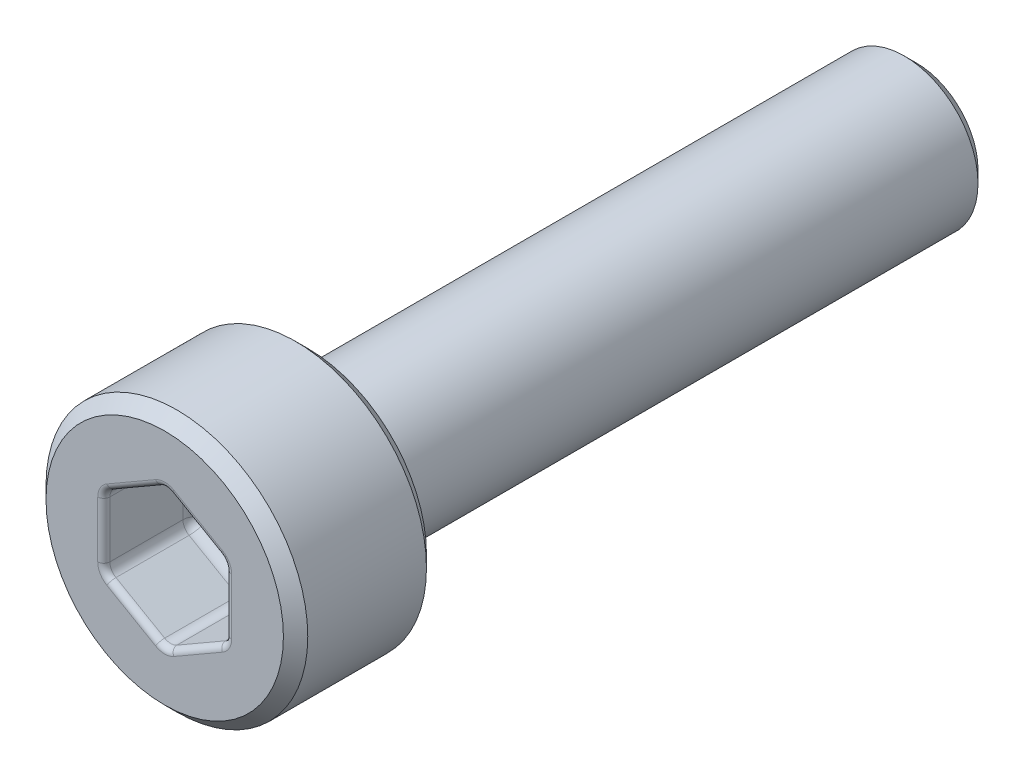
SolidWorks part; units mm, degrees
material "1.4000 (X6Cr13)"
ref_plane "Ebene vorne" through (0, 0, 0) normal (0, 0, 1) x (1, 0, 0)
ref_plane "Ebene oben" through (0, 0, 0) normal (0, 1, 0) x (1, 0, 0)
ref_plane "Ebene rechts" through (0, 0, 0) normal (1, 0, 0) x (0, 0, -1)
sketch "Skizze1" plane through (0, 0, 0) normal (1, 0, 0) x (0, 0, -1)
  line L0 (-21.9199, 0) -> (33.7608, 0) construction
  line L1 (0, 13.9907) -> (0, -9.4798) construction
  line L2 (-2.35, 0) -> (-2.35, 2.15)
  line L3 (-2.35, 2.15) -> (0, 2.15)
  line L4 (0, 2.15) -> (0, 1.21)
  line L5 (0, 1.21) -> (10, 1.21)
  line L6 (10, 1.21) -> (10, 0)
  line L7 (10, 0) -> (-2.35, 0)
  dimension "D1" = 2.42
  dimension "D2" = 2.35
  dimension "D3" = 4.3
  dimension "D4" = 10
revolve "Rotation1" add sketch "Skizze1" angle 360 about L0
sketch "Skizze2" plane through (0, 0, 2.35) normal (0, 0, 1) x (1, 0, 0)
  line L0 (0, 8.6995) -> (0, -7.3778) construction
  line L1 (1, -0.5774) -> (1, 0.5774)
  line L2 (1, 0.5774) -> (0, 1.1547)
  line L3 (0, 1.1547) -> (-1, 0.5774)
  line L4 (-1, 0.5774) -> (-1, -0.5774)
  line L5 (-1, -0.5774) -> (0, -1.1547)
  line L6 (0, -1.1547) -> (1, -0.5774)
  circle A0 centre (0, 0) radius 1 construction
  dimension "D1" = 2
extrude "Schnitt-Linear austragen1" cut sketch "Skizze2" against normal blind 1.5
chamfer "Fase1" distance 0.2 angle 45 3 edges at (2.15, 0, 2.35) (2.15, 0, 0) (1.21, 0, -10)
fillet "Verrundung1" radius 0.2 13 edges at (-0.5, -0.866, 0.85) (-1, 0, 0.85) (-0.5, 0.866, 0.85) (0.5, 0.866, 0.85) (1, 0, 0.85) (0.5, -0.866, 0.85) (-1, -0.5774, 1.6) (0, -1.1547, 1.6) (1, -0.5774, 1.6) (1, 0.5774, 1.6) (0, 1.1547, 1.6) (-1, 0.5774, 1.6) (1.21, 0, 0)
fillet "Verrundung2" radius 0.1 12 edges at (0.9732, -0.5619, 2.35) (0.5, -0.866, 2.35) (0, -1.1238, 2.35) (-0.5, -0.866, 2.35) (-0.9732, -0.5619, 2.35) (-1, 0, 2.35) (-0.9732, 0.5619, 2.35) (-0.5, 0.866, 2.35) (0, 1.1238, 2.35) (0.5, 0.866, 2.35) (0.9732, 0.5619, 2.35) (1, 0, 2.35)
ref_axis "Achse1" through (0, 0, -19.6323) along (0, 0, 1)
